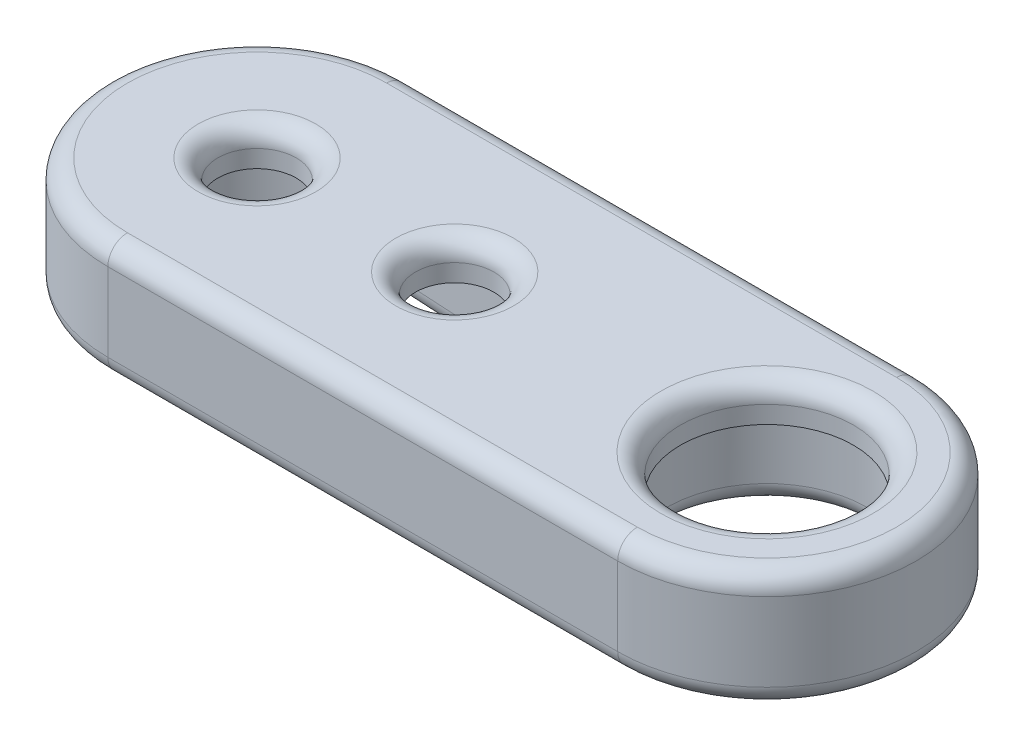
SolidWorks part; units mm, degrees
ref_plane "Front Plane" through (0, 0, 0) normal (0, 0, 1) x (1, 0, 0)
ref_plane "Top Plane" through (0, 0, 0) normal (0, 1, 0) x (1, 0, 0)
ref_plane "Right Plane" through (0, 0, 0) normal (1, 0, 0) x (0, 0, -1)
sketch "Sketch1" plane through (0, 0, 0) normal (0, 1, 0) x (1, 0, 0)
  line L0 (2.2864, 2.65) -> (14.1103, 1.997)
  line L1 (2.2864, -2.65) -> (14.1103, -1.997)
  line L2 (0, 0) -> (14, 0) construction
  line L4 (0, 6.04) -> (20.6375, 6.04)
  line L8 (0, -6.04) -> (20.6375, -6.04)
  circle A0 centre (0, 0) radius 3.5 construction
  arc A1 (14.1103, 1.997) -> (14.1103, -1.997) centre (14, 0) cw
  arc A2 (2.2864, 2.65) -> (2.2864, -2.65) centre (0, 0) ccw
  circle A3 centre (14, 0) radius 0.5 construction
  circle A4 centre (12, 0) radius 0.5 construction
  circle A5 centre (10, 0) radius 0.5 construction
  circle A6 centre (8, 0) radius 0.5 construction
  circle A7 centre (6, 0) radius 0.5 construction
  circle A8 centre (4, 0) radius 0.5 construction
  arc A12 (0, -6.04) -> (0, 6.04) centre (0, 0) cw
  circle A17 centre (20.6375, 0) radius 4.064
  arc A18 (20.6375, -6.04) -> (20.6375, 6.04) centre (20.6375, 0) ccw
  point P4 (16, 0)
  point P6 (-3.5, 0)
  dimension "D1" = 7
  dimension "D5" = 1
  dimension "D8" = 2.54
  dimension "D10" = 20.6375
  dimension "D4" = 2
  dimension "D9" = 8.128
  dimension "D2" = 19.5
  dimension "D3" = 5.3
  dimension "D7" = 2
  dimension "D6" = 6
extrude "Boss-Extrude1" add sketch "Sketch1" along normal blind 4.5
sketch "Sketch2" plane through (0, 4.5, 0) normal (0, 1, 0) x (1, 0, 0)
  line L0 (0, 0) -> (16, 0) construction
  line L4 (20.6375, 6.04) -> (0, 6.04)
  line L5 (0, -6.04) -> (20.6375, -6.04)
  line L8 (20.6375, 6.04) -> (0, 6.04)
  line L9 (0, -6.04) -> (20.6375, -6.04)
  circle A0 centre (0, 0) radius 1.5875
  circle A1 centre (8, 0) radius 1.5875
  arc A2 (14.1103, -1.997) -> (14.1103, 1.997) centre (14, 0) ccw construction
  circle A3 centre (20.6375, 0) radius 3.5
  arc A5 (20.6375, -6.04) -> (20.6375, 6.04) centre (20.6375, 0) ccw
  arc A6 (20.6375, -6.04) -> (20.6375, 6.04) centre (20.6375, 0) ccw
  arc A9 (0, 6.04) -> (0, -6.04) centre (0, 0) ccw
  arc A17 (0, 6.04) -> (0, -6.04) centre (0, 0) ccw
  point P15 (8, 0)
  dimension "D2" = 3.175
  dimension "D3" = 3.175
  dimension "D4" = 7
  dimension "D1" = 0
extrude "Boss-Extrude2" add sketch "Sketch2" along normal offset from surface (1.5 mm away) 6 up to face at (7.2242, 0, 0)
sketch "Sketch3" plane through (0, 0, 0) normal (0, -1, 0) x (1, 0, 0)
  line L6 (20.6375, 6.04) -> (0, 6.04)
  line L7 (0, -6.04) -> (20.6375, -6.04)
  line L10 (20.6375, 6.04) -> (0, 6.04)
  line L11 (0, -6.04) -> (20.6375, -6.04)
  arc A2 (20.6375, -6.04) -> (20.6375, 6.04) centre (20.6375, 0) ccw
  arc A3 (20.6375, -6.04) -> (20.6375, 6.04) centre (20.6375, 0) ccw
  arc A11 (0, 6.04) -> (0, -6.04) centre (0, 0) ccw
  arc A17 (0, 6.04) -> (0, -6.04) centre (0, 0) ccw
  dimension "D1" = 0
extrude "Cut-Extrude1" cut sketch "Sketch3" against normal offset from surface (1.2375 mm away) 4.7625
fillet "Fillet2" radius 0.7937 9 edges at (10.3187, 1.2375, -6.04) (-6.04, 1.2375, 0) (10.3187, 1.2375, 6.04) (-3.5, 1.2375, 0) (8.1983, 1.2375, -2.3235) (16, 1.2375, 0) (8.1983, 1.2375, 2.3235) (26.6775, 1.2375, 0) (20.6375, 1.2375, -4.064)
fillet "Fillet3" radius 0.7937 7 edges at (10.3187, 6, 6.04) (-6.04, 6, 0) (10.3187, 6, -6.04) (0, 6, -1.5875) (8, 6, -1.5875) (26.6775, 6, 0) (20.6375, 6, -3.5)
